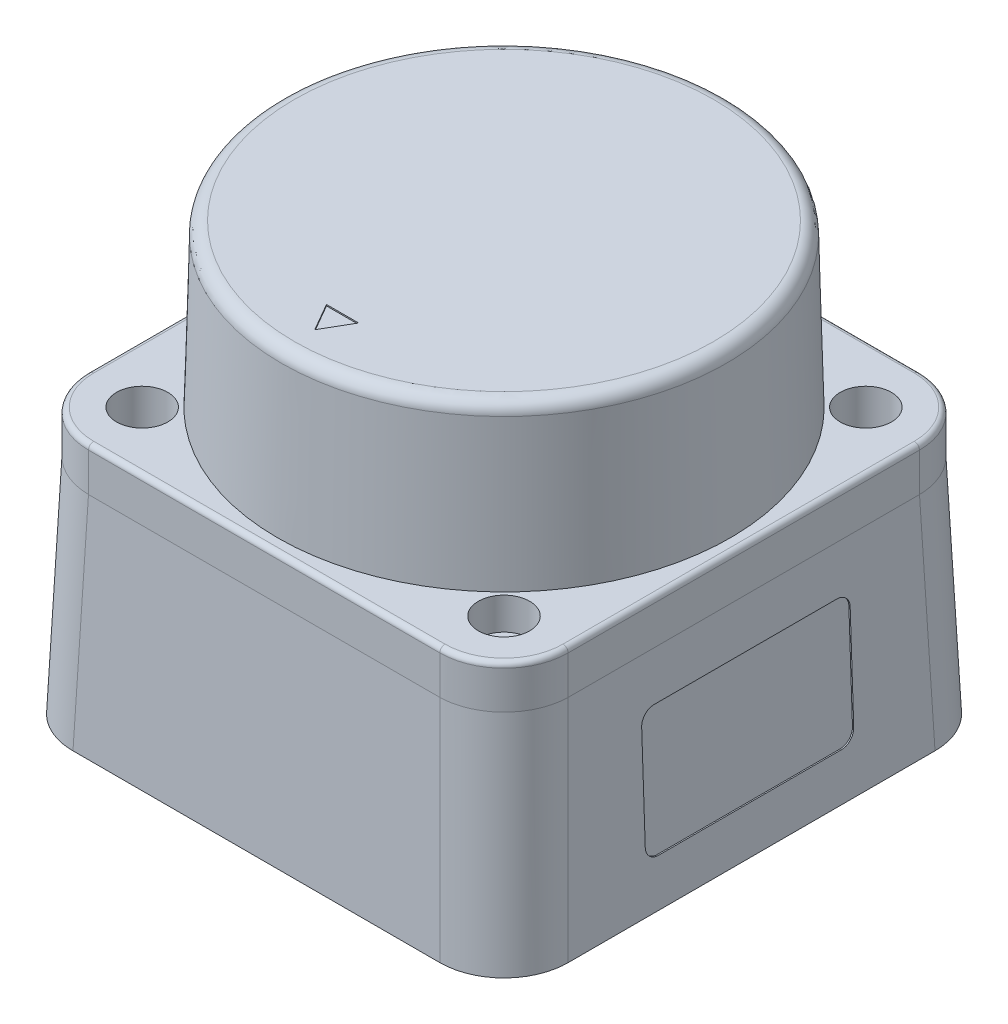
SolidWorks part; units mm, degrees
ref_plane "Front Plane" through (0, 0, 0) normal (0, 0, 1) x (1, 0, 0)
ref_plane "Top Plane" through (0, 0, 0) normal (0, 1, 0) x (1, 0, 0)
ref_plane "Right Plane" through (0, 0, 0) normal (1, 0, 0) x (0, 0, -1)
sketch "Sketch1" plane through (0, 0, 0) normal (0, 1, 0) x (1, 0, 0)
  line L0 (-19.295, 0) -> (19.295, 0) construction
  line L1 (-19.295, 19.295) -> (19.295, 19.295)
  line L2 (-19.295, 19.295) -> (-19.295, -19.295)
  line L3 (-19.295, -19.295) -> (19.295, -19.295)
  line L4 (19.295, 19.295) -> (19.295, -19.295)
  line L5 (0, 19.295) -> (0, -19.295) construction
  point P8 (0, 0)
  dimension "D1" = 38.59
  dimension "D2" = 38.59
extrude "Boss-Extrude1" add sketch "Sketch1" along normal blind 17.3 draft 2
sketch "Sketch2" plane through (0, 17.3, 0) normal (0, 1, 0) x (1, 0, 0)
  line L0 (0, 18.6909) -> (0, -18.6909) construction
  line L1 (-18.6909, 18.6909) -> (18.6909, 18.6909)
  line L2 (-18.6909, 18.6909) -> (-18.6909, -18.6909)
  line L3 (-18.6909, -18.6909) -> (18.6909, -18.6909)
  line L4 (18.6909, 18.6909) -> (18.6909, -18.6909)
  line L5 (-18.6909, 0) -> (18.6909, 0) construction
  line L6 (18.6909, -18.6909) -> (18.6909, 18.6909) construction
  line L7 (18.6909, 18.6909) -> (-18.6909, 18.6909) construction
  point P8 (0, 0)
extrude "Boss-Extrude2" add sketch "Sketch2" along normal blind 3.4
sketch "Sketch3" plane through (0, 20.7, 0) normal (0, 1, 0) x (1, 0, 0)
  circle A0 centre (0, 0) radius 17.645
  dimension "D1" = 35.29
extrude "Boss-Extrude3" add sketch "Sketch3" along normal blind 12.6 draft 1.5 contours A0
fillet "Fillet1" radius 5 8 edges at (-18.9929, 8.65, -18.9929) (-18.6909, 19, -18.6909) (18.6909, 19, -18.6909) (18.9929, 8.65, -18.9929) (-18.9929, 8.65, 18.9929) (-18.6909, 19, 18.6909) (18.9929, 8.65, 18.9929) (18.6909, 19, 18.6909)
fillet "Fillet2" radius 0.4 8 edges at (17.2264, 20.7, -17.2264) (0, 20.7, -18.6909) (18.6909, 20.7, 0) (17.2264, 20.7, 17.2264) (0, 20.7, 18.6909) (-17.2264, 20.7, 17.2264) (-18.6909, 20.7, 0) (-17.2264, 20.7, -17.2264)
fillet "Fillet3" radius 1 1 edges at (0, 33.3, 17.3151)
sketch "Sketch4" plane through (0, 33.3, 0) normal (0, 1, 0) x (1, 0, 0)
  line L1 (0, -14.75) -> (1.25, -12.5849)
  line L2 (1.25, -12.5849) -> (-1.25, -12.5849)
  line L3 (-1.25, -12.5849) -> (0, -14.75)
  circle A0 centre (0, -13.3066) radius 1.4434 construction
  dimension "D1" = 14.75
  dimension "D2" = 2.5
extrude "Cut-Extrude1" cut sketch "Sketch4" against normal blind 0.1
sketch "Sketch5" plane through (0, 0, 0) normal (0, 0, 1) x (1, 0, 0)
  line L0 (16.3409, 33.3) -> (-16.3409, 33.3) construction
  circle A0 centre (0, 25.7) radius 4
  dimension "D1" = 7.6
  dimension "D2" = 8
extrude "Cut-Extrude2" [suppressed] cut sketch "Sketch5" against normal blind 0.01 from surface
sketch "Sketch6" plane through (0, 0, 0) normal (1, 0, 0) x (0, 0, -1)
  line L0 (-4.625, 3.725) -> (4.625, 3.725) construction
  line L1 (-4.625, 5.85) -> (4.625, 5.85)
  line L2 (-4.625, 5.85) -> (-4.625, 1.6)
  line L3 (-4.625, 1.6) -> (4.625, 1.6)
  line L4 (4.625, 5.85) -> (4.625, 1.6)
  line L5 (0, 5.85) -> (0, 1.6) construction
  line L6 (-14.298, 0) -> (14.298, 0) construction
  point P8 (0, 3.725)
  dimension "D1" = 9.25
  dimension "D2" = 4.25
  dimension "D3" = 1.6
extrude "Cut-Extrude3" cut sketch "Sketch6" along normal blind 7 from offset 19.295 offset against normal yes
sketch "Sketch15" plane through (0, 0, 0) normal (1, 0, 0) x (0, 0, -1)
  line L0 (-8.125, 8.6) -> (8.125, 8.6) construction
  line L1 (-8.125, 13.6) -> (8.125, 13.6)
  line L2 (-8.125, 13.6) -> (-8.125, 3.6)
  line L3 (-8.125, 3.6) -> (8.125, 3.6)
  line L4 (8.125, 13.6) -> (8.125, 3.6)
  line L5 (0, 13.6) -> (0, 3.6) construction
  line L6 (-14.298, 0) -> (14.298, 0) construction
  point P8 (0, 8.6)
  dimension "D1" = 3.6
  dimension "D2" = 10
  dimension "D3" = 16.25
extrude "Cut-Extrude4" cut sketch "Sketch15" against normal blind 0.1 from surface starting at face at (18.8922, 11.5333, 0)
fillet "Fillet4" radius 1 4 edges at (19.1193, 3.6, -8.125) (18.7701, 13.6, -8.125) (18.7701, 13.6, 8.125) (19.1193, 3.6, 8.125)
sketch "Sketch10" plane through (0, 20.7, 0) normal (0, 1, 0) x (1, 0, 0)
  line L0 (0, 18.2909) -> (0, -18.2909) construction
  line L1 (13.6909, 18.2909) -> (-13.6909, 18.2909) construction
  line L2 (-13.6909, -18.2909) -> (13.6909, -18.2909) construction
  line L3 (18.2909, 0) -> (-18.2909, 0) construction
  line L4 (18.2909, -13.6909) -> (18.2909, 13.6909) construction
  line L5 (-18.2909, 13.6909) -> (-18.2909, -13.6909) construction
  circle A0 centre (-14.1, 14.1) radius 2
  circle A1 centre (14.1, -14.1) radius 2
  dimension "D1" = 14.1
  dimension "D5" = 4
  dimension "D2" = 14.1
  dimension "D3" = 14.1
  dimension "D4" = 14.1
extrude "Cut-Extrude5" cut sketch "Sketch10" against normal blind 2.5
sketch "Sketch12" plane through (0, 18.2, 0) normal (0, 1, 0) x (1, 0, 0)
  circle A0 centre (14.1, -14.1) radius 1
  circle A1 centre (-14.1, 14.1) radius 1
  circle A2 centre (-14.1, 14.1) radius 2 construction
  circle A3 centre (14.1, -14.1) radius 2 construction
  dimension "D1" = 2
extrude "Cut-Extrude6" cut sketch "Sketch12" against normal blind 6
sketch "Sketch7" plane through (0, 20.7, 0) normal (0, 1, 0) x (1, 0, 0)
  line L0 (0, 18.2909) -> (0, -18.2909) construction
  line L1 (13.6909, 18.2909) -> (-13.6909, 18.2909) construction
  line L2 (-13.6909, -18.2909) -> (13.6909, -18.2909) construction
  line L3 (18.2909, 0) -> (-18.2909, 0) construction
  line L4 (18.2909, -13.6909) -> (18.2909, 13.6909) construction
  line L5 (-18.2909, 13.6909) -> (-18.2909, -13.6909) construction
  circle A0 centre (-14.1, -14.1) radius 2
  circle A1 centre (14.1, 14.1) radius 2
  dimension "D1" = 4
  dimension "D3" = 14.1
  dimension "D4" = 14.1
  dimension "D5" = 14.1
  dimension "D6" = 14.1
extrude "Cut-Extrude7" cut sketch "Sketch7" against normal blind 7.9
sketch "Sketch13" plane through (0, 12.8, 0) normal (0, 1, 0) x (1, 0, 0)
  circle A0 centre (-14.1, -14.1) radius 1.25
  circle A1 centre (-14.1, -14.1) radius 2 construction
  circle A2 centre (14.1, 14.1) radius 1.25
  circle A3 centre (14.1, 14.1) radius 2 construction
  dimension "D1" = 2.5
extrude "Cut-Extrude8" cut sketch "Sketch13" against normal blind 1
sketch "Sketch14" plane through (0, 11.8, 0) normal (0, 1, 0) x (1, 0, 0)
  circle A0 centre (-14.1, -14.1) radius 2.4
  circle A1 centre (-14.1, -14.1) radius 1.25 construction
  circle A2 centre (14.1, 14.1) radius 2.4
  circle A3 centre (14.1, 14.1) radius 1.25 construction
  dimension "D1" = 4.8
extrude "Cut-Extrude9" cut sketch "Sketch14" against normal blind 11.8
sketch "Sketch16" plane through (0, 0, 0) normal (0, -1, 0) x (1, 0, 0)
  line L0 (0, 19.295) -> (0, -19.295) construction
  line L1 (-14.298, 19.295) -> (14.298, 19.295) construction
  line L2 (14.298, -19.295) -> (-14.298, -19.295) construction
  line L3 (19.295, 0) -> (-19.295, 0) construction
  line L4 (19.295, 14.298) -> (19.295, -14.298) construction
  line L5 (-19.295, -14.298) -> (-19.295, 14.298) construction
  circle A0 centre (-15.7, -15.7) radius 1.25
  dimension "D1" = 2.5
  dimension "D2" = 15.7
  dimension "D3" = 15.7
extrude "Cut-Extrude10" cut sketch "Sketch16" against normal blind 5.8
